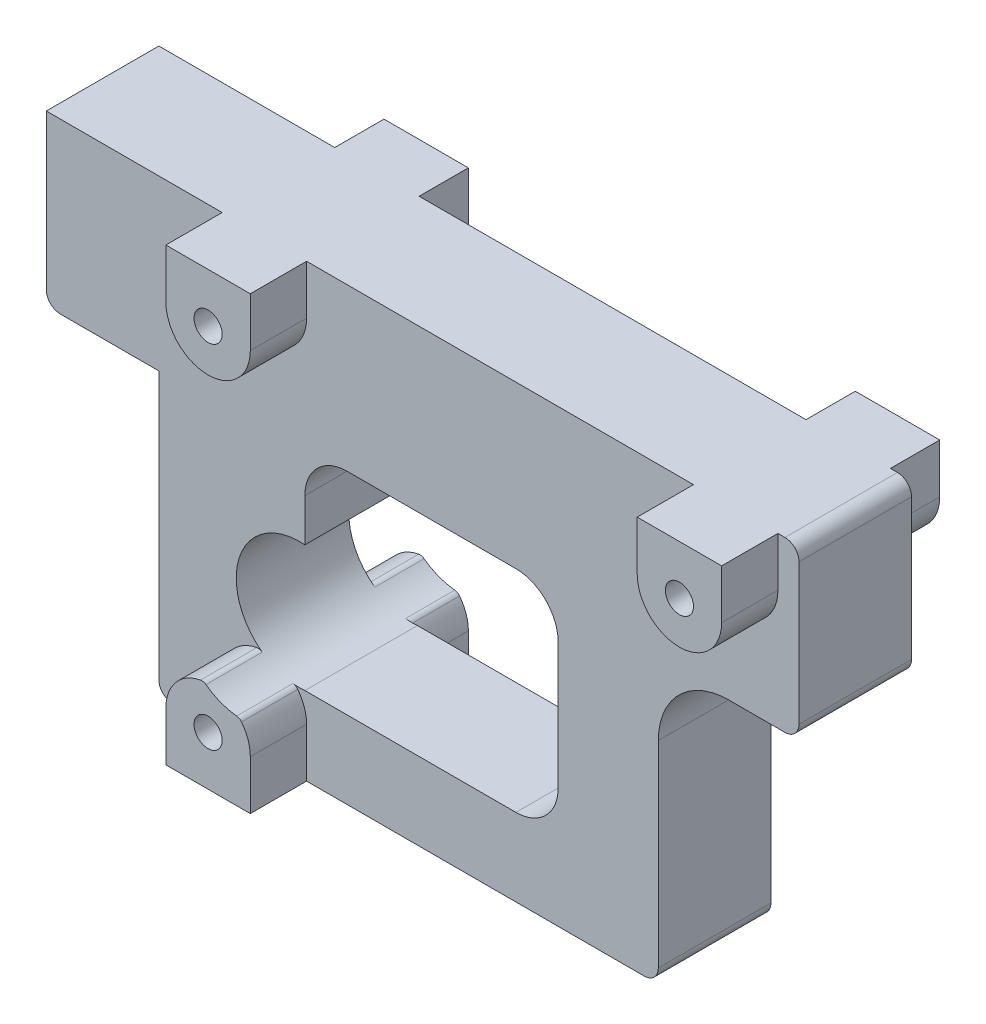
SolidWorks part; units mm, degrees
ref_plane "Спереди" through (0, 0, 0) normal (0, 0, 1) x (1, 0, 0)
ref_plane "Сверху" through (0, 0, 0) normal (0, 1, 0) x (1, 0, 0)
ref_plane "Справа" through (0, 0, 0) normal (1, 0, 0) x (0, 0, -1)
sketch "Эскиз2" plane through (0, 0, 0) normal (0, 0, 1) x (1, 0, 0)
  line L1 (-18.8586, 18.0445) -> (33.6414, 18.0445)
  line L2 (-18.8586, 18.0445) -> (-18.8586, 7.0445)
  line L3 (-9.8586, -13.9555) -> (23.6414, -13.9555)
  line L4 (34.6414, 17.0445) -> (34.6414, 7.0445)
  line L7 (33.6414, 6.0445) -> (29.6414, 6.0445)
  line L8 (24.6414, -12.9555) -> (24.6414, 1.0445)
  line L11 (-17.8586, 6.0445) -> (-10.8586, 6.0445)
  line L12 (-10.8586, -12.9555) -> (-10.8586, 6.0445)
  circle A0 centre (-0.8586, -3.9555) radius 4.5
  arc A1 (29.6414, 6.0445) -> (24.6414, 1.0445) centre (29.6414, 1.0445) ccw
  arc A2 (-17.8586, 6.0445) -> (-18.8586, 7.0445) centre (-17.8586, 7.0445) cw
  arc A3 (33.6414, 18.0445) -> (34.6414, 17.0445) centre (33.6414, 17.0445) cw
  arc A4 (33.6414, 6.0445) -> (34.6414, 7.0445) centre (33.6414, 7.0445) ccw
  arc A5 (-9.8586, -13.9555) -> (-10.8586, -12.9555) centre (-9.8586, -12.9555) cw
  arc A6 (23.6414, -13.9555) -> (24.6414, -12.9555) centre (23.6414, -12.9555) ccw
  point P12 (24.6414, 6.0445)
  point P15 (-18.8586, 6.0445)
  point P18 (34.6414, 18.0445)
  point P21 (34.6414, 6.0445)
  point P24 (-10.8586, -13.9555)
  point P27 (24.6414, -13.9555)
  dimension "D8" = 9
  dimension "D9" = 5
  dimension "D10" = 1
  dimension "D1" = 53.5
  dimension "D2" = 22
  dimension "D3" = 20
  dimension "D4" = 10
  dimension "D5" = 8
  dimension "D6" = 20
  dimension "D7" = 18
extrude "Бобышка-Вытянуть1" add sketch "Эскиз2" along normal blind 8
sketch "Эскиз3" plane through (0, 0, 8) normal (0, 0, 1) x (1, 0, 0)
  line L0 (-18.8586, 18.0445) -> (-18.8586, 7.0445) construction
  line L2 (33.6414, 18.0445) -> (-18.8586, 18.0445) construction
  line L3 (27.1414, 14.5445) -> (27.1414, 18.0445)
  line L4 (33.1414, 14.5445) -> (33.1414, 18.0445)
  line L5 (33.1414, 18.0445) -> (27.1414, 18.0445)
  line L6 (-0.3586, 14.5445) -> (-0.3586, 18.0445)
  line L7 (-6.3586, 14.5445) -> (-6.3586, 18.0445)
  line L8 (-6.3586, 18.0445) -> (-0.3586, 18.0445)
  line L9 (-6.3586, -10.4555) -> (-6.3586, -13.9555)
  line L10 (-9.8586, -13.9555) -> (23.6414, -13.9555) construction
  line L11 (-0.3586, -10.4555) -> (-0.3586, -13.9555)
  line L12 (-0.3586, -13.9555) -> (-6.3586, -13.9555)
  circle A0 centre (-3.3586, 14.5445) radius 1.5 construction
  circle A1 centre (30.1414, 14.5445) radius 1.5 construction
  circle A2 centre (-3.3586, -10.4555) radius 1.5 construction
  arc A3 (27.1414, 14.5445) -> (33.1414, 14.5445) centre (30.1414, 14.5445) ccw
  arc A4 (-6.3586, 14.5445) -> (-0.3586, 14.5445) centre (-3.3586, 14.5445) ccw
  arc A5 (-0.3586, -10.4555) -> (-0.9834, -8.6229) centre (-3.3586, -10.4555) ccw
  arc A6 (-3.5098, -7.5915) -> (-1.3272, -8.431) centre (-0.8586, -3.9555) ccw
  arc A7 (-3.8935, -7.5036) -> (-6.3586, -10.4555) centre (-3.3586, -10.4555) ccw
  arc A8 (-0.9834, -8.6229) -> (-1.3272, -8.431) centre (-1.3792, -8.9283) ccw
  arc A9 (-3.5098, -7.5915) -> (-3.8935, -7.5036) centre (-3.8044, -7.9955) ccw
  point P32 (-3.6672, -7.4714)
  dimension "D3" = 3
  dimension "D4" = 33.5
  dimension "D6" = 6
  dimension "D7" = 9
  dimension "D8" = 0.5
  dimension "D1" = 15.5
  dimension "D2" = 3.5
  dimension "D5" = 25
extrude "Бобышка-Вытянуть2" add sketch "Эскиз3" along normal blind 4 and the other way blind 11.5
sketch "Эскиз5" plane through (0, 0, 8) normal (0, 0, 1) x (1, 0, 0)
  line L1 (14.5209, 6.5605) -> (2.5209, 6.5605)
  line L2 (17.5209, 3.5605) -> (17.5209, -5.4395)
  line L3 (14.5209, -8.4395) -> (-0.4791, -8.4395)
  line L4 (-0.4791, 3.5605) -> (-0.4791, -8.4395)
  arc A0 (-1.3272, -8.431) -> (-3.5098, -7.5915) centre (-0.8586, -3.9555) ccw construction
  arc A1 (14.5209, -8.4395) -> (17.5209, -5.4395) centre (14.5209, -5.4395) ccw
  arc A2 (17.5209, 3.5605) -> (14.5209, 6.5605) centre (14.5209, 3.5605) ccw
  arc A3 (-0.4791, 3.5605) -> (2.5209, 6.5605) centre (2.5209, 3.5605) cw
  point P9 (17.5209, -8.4395)
  point P12 (17.5209, 6.5605)
  dimension "D3" = 3
  dimension "D1" = 15
  dimension "D2" = 18
extrude "Вырез-Вытянуть1" cut sketch "Эскиз5" against normal through all both and the other way through all
sketch "Эскиз6" plane through (0, 0, 8) normal (0, 0, 1) x (1, 0, 0)
  circle A0 centre (-3.3586, 14.5445) radius 1
  circle A1 centre (30.1414, 14.5445) radius 1
  circle A2 centre (-3.3586, -10.4555) radius 1
  dimension "D1" = 2
extrude "Вырез-Вытянуть2" cut sketch "Эскиз6" against normal through all both and the other way through all
